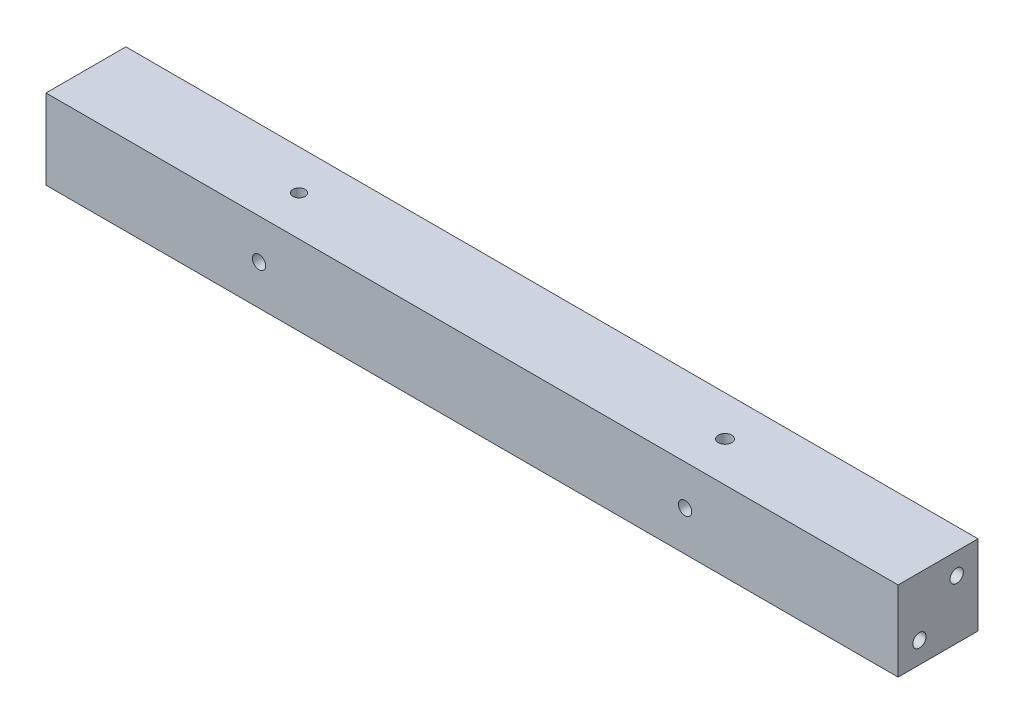
SolidWorks part; units mm, degrees
ref_plane "Ön Düzlem" through (0, 0, 0) normal (0, 0, 1) x (1, 0, 0)
ref_plane "Üst Düzlem" through (0, 0, 0) normal (0, 1, 0) x (1, 0, 0)
ref_plane "Sağ Düzlem" through (0, 0, 0) normal (1, 0, 0) x (0, 0, -1)
sketch "Sketch1" plane through (0, 0, 0) normal (0, 0, 1) x (1, 0, 0)
  line L1 (0, 0) -> (160, 0)
  line L2 (0, 0) -> (0, 15)
  line L3 (0, 15) -> (160, 15)
  line L4 (160, 0) -> (160, 15)
extrude "Boss-Extrude1" add sketch "Sketch1" along normal blind 15
sketch "Sketch2" plane through (0, 0, 15) normal (0, 0, 1) x (1, 0, 0)
  line L0 (0, 15) -> (0, 0) construction
  line L1 (160, 15) -> (0, 15) construction
  line L2 (160, 0) -> (160, 15) construction
  circle A0 centre (40, 7.5) radius 1.25
  circle A1 centre (120, 7.5) radius 1.25
  dimension "D1" = 40
  dimension "D2" = 7.5
  dimension "D3" = 40
  dimension "D4" = 7.5
extrude "Cut-Extrude1" cut sketch "Sketch2" against normal blind 5
cosmetic thread "Cosmetic Thread1" parameters "D2"=3
cosmetic thread "Cosmetic Thread2" parameters "D2"=3
sketch "Sketch3" plane through (0, 15, 0) normal (0, 1, 0) x (1, 0, 0)
  line L0 (0, -15) -> (0, 0) construction
  line L1 (160, 0) -> (0, 0) construction
  line L2 (160, -15) -> (160, 0) construction
  circle A0 centre (40, -7.5) radius 1.145
  circle A1 centre (120, -7.5) radius 1.25
  dimension "D1" = 40
  dimension "D2" = 7.5
  dimension "D3" = 40
  dimension "D4" = 7.5
extrude "Cut-Extrude2" cut sketch "Sketch3" against normal blind 5
cosmetic thread "Cosmetic Thread3" parameters "D2"=3
cosmetic thread "Cosmetic Thread4" parameters "D2"=3
sketch "Sketch4" plane through (0, 0, 0) normal (0, 0, -1) x (-1, 0, 0)
  line L0 (-160, 0) -> (-160, 15) construction
  line L1 (-160, 15) -> (0, 15) construction
  line L2 (0, 15) -> (0, 0) construction
  circle A0 centre (-120, 7.5) radius 1.25
  circle A1 centre (-40, 7.5) radius 1.25
  dimension "D1" = 40
  dimension "D2" = 7.5
  dimension "D3" = 7.5
  dimension "D4" = 40
extrude "Cut-Extrude3" cut sketch "Sketch4" against normal blind 5
cosmetic thread "Cosmetic Thread5" parameters "D2"=3
cosmetic thread "Cosmetic Thread6" parameters "D2"=3
sketch "Sketch5" plane through (0, 0, 0) normal (0, -1, 0) x (1, 0, 0)
  line L0 (0, 15) -> (0, 0) construction
  line L1 (0, 15) -> (160, 15) construction
  line L2 (160, 15) -> (160, 0) construction
  circle A0 centre (40, 7.5) radius 1.25
  circle A1 centre (120, 7.5) radius 1.25
  dimension "D1" = 40
  dimension "D2" = 7.5
  dimension "D3" = 7.5
  dimension "D4" = 40
extrude "Cut-Extrude4" cut sketch "Sketch5" against normal blind 5
cosmetic thread "Cosmetic Thread7" parameters "D2"=3
cosmetic thread "Cosmetic Thread8" parameters "D2"=3
sketch "Sketch6" plane through (0, 0, 0) normal (-1, 0, 0) x (0, 0, 1)
  line L0 (0, 15) -> (15, 0) construction
  line L1 (0, 15) -> (0, 0) construction
  line L4 (15, 15) -> (15, 0) construction
  circle A0 centre (4, 11) radius 1.25
  circle A1 centre (11, 4) radius 1.25
  dimension "D1" = 4
  dimension "D2" = 4
extrude "Cut-Extrude5" cut sketch "Sketch6" against normal blind 10
cosmetic thread "Cosmetic Thread9" parameters "D2"=3
cosmetic thread "Cosmetic Thread10" parameters "D2"=3
sketch "Sketch7" plane through (160, 0, 0) normal (1, 0, 0) x (0, 0, -1)
  line L0 (0, 15) -> (-15, 0) construction
  line L1 (0, 0) -> (0, 15) construction
  line L2 (-15, 0) -> (-15, 15) construction
  circle A0 centre (-4, 11) radius 1.25
  circle A1 centre (-11, 4) radius 1.25
  dimension "D1" = 4
  dimension "D2" = 4
extrude "Cut-Extrude6" cut sketch "Sketch7" against normal blind 10
